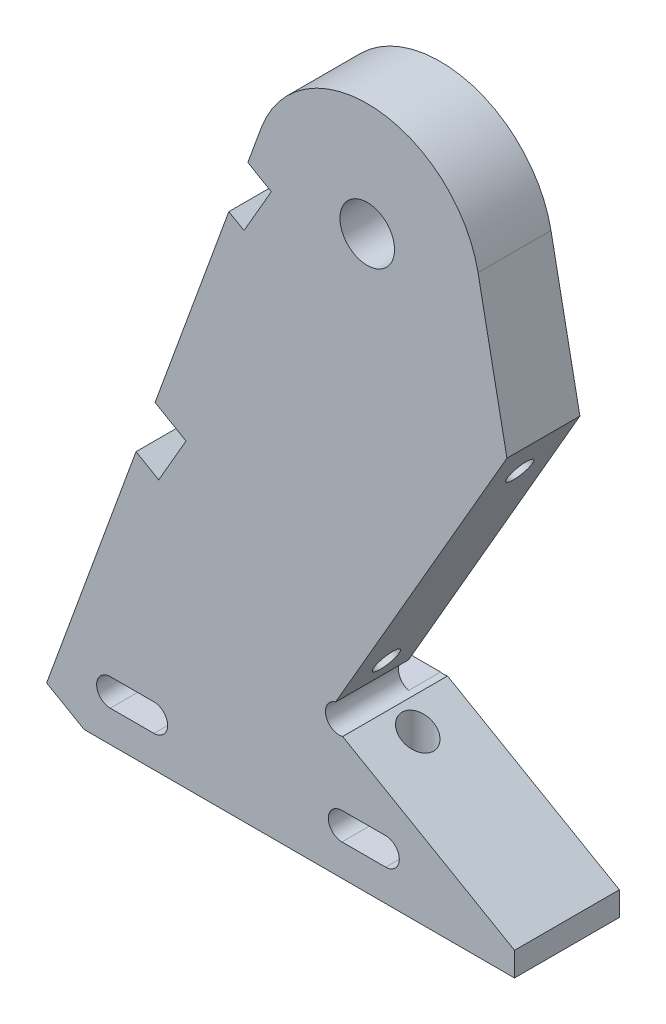
SolidWorks part; units mm, degrees
ref_plane "Front Plane" through (0, 0, 0) normal (0, 0, 1) x (1, 0, 0)
ref_plane "Top Plane" through (0, 0, 0) normal (0, 1, 0) x (1, 0, 0)
ref_plane "Right Plane" through (0, 0, 0) normal (1, 0, 0) x (0, 0, -1)
sketch "Model" plane through (0, 0, 0) normal (0, 0, 1) x (1, 0, 0)
  line L0 (30.032, -29.5212) -> (30.032, -26.7298)
  line L1 (-3.1895, 31.0479) -> (-11.7681, 7.5374)
  line L2 (12.4426, -6.5562) -> (9.2271, -12.1257) construction
  line L3 (16.6788, -19.0204) -> (10.0488, -15.1925) construction
  line L4 (9.6915, -11.3213) -> (10.8533, -15.657) construction
  line L5 (10.2724, -13.4891) -> (9.0035, -13.8291) construction
  line L6 (29.1519, 22.385) -> (9.2271, -12.1257)
  line L7 (30.032, -26.7298) -> (10.0488, -15.1925)
  line L8 (9.3745, -14.8032) -> (2.5284, -10.8506) construction
  line L9 (9.0235, -12.4784) -> (5.2305, -19.0481) construction
  line L10 (0.5709, 41.3535) -> (-0.9796, 37.1044)
  line L11 (0.0253, 32.858) -> (-15.4747, 6.0112) construction
  line L12 (-11.7681, 7.5374) -> (-8.1659, 5.4577)
  line L13 (-15.4747, 6.0112) -> (10.9052, -9.2192) construction
  line L14 (-11.7681, 7.5374) -> (-13.8872, 8.7609) construction
  line L15 (-11.3408, -0.0416) -> (-13.978, 1.4809) construction
  line L16 (-8.1659, 5.4577) -> (-11.3408, -0.0416)
  line L17 (-11.3408, -0.0416) -> (-13.978, 1.4809)
  line L18 (-13.978, 1.4809) -> (-24.3737, -27.0097)
  line L19 (0.0253, 32.858) -> (26.4052, 17.6276) construction
  line L20 (-1.4214, 30.0271) -> (1.7536, 35.5264)
  line L21 (-0.9796, 37.1044) -> (1.7536, 35.5264)
  line L22 (-3.1895, 31.0479) -> (-1.4214, 30.0271)
  line L23 (11.3113, 26.3421) -> (-4.1887, -0.5047) construction
  line L24 (3.5613, 12.9187) -> (-2.5691, 16.458) construction
  line L25 (12.2357, 35.6885) -> (0.2074, 14.855) construction
  line L26 (0.2074, 14.855) -> (12.9074, 36.8521) construction
  line L28 (29.1519, 22.385) -> (25.7905, 39.3975)
  line L80 (-20.0226, -29.5212) -> (-24.3737, -27.0097)
  line L82 (30.032, -29.5212) -> (-20.0226, -29.5212)
  circle A0 centre (12.9074, 36.8521) radius 3.175
  arc A2 (9.2271, -12.1257) -> (10.0488, -15.1925) centre (9.638, -13.6591) ccw
  arc A3 (25.7905, 39.3975) -> (0.5709, 41.3535) centre (12.9074, 36.8521) ccw
  point P11 (8.1045, -14.07)
  point P12 (8.1045, -14.07)
  point P37 (0.1661, 32.7767)
  dimension "D1" = 3.175
  dimension "D7" = 6.35
  dimension "D2" = 31
  dimension "D3" = 3.175
  dimension "D4" = 3.175
  dimension "D5" = 6.35
  dimension "D6" = 25.4
extrude "Boss-Extrude1" add sketch "Model" along normal blind 8.4836
hole_wizard "#4 Clearance Hole3" positions "Sketch8" profile "Sketch9" hole size "#4" standard "ANSI Inch" end condition through all
sketch "Sketch8" plane through (-14.0682, 8.1223, 0) normal (-0.866, 0.5, 0) x (0, 0, 1)
  line L0 (8.4836, 25.2935) -> (0, 31.6435) construction
  point P7 (4.2418, 28.4685)
sketch "Sketch9" plane through (0.1661, 32.7767, 4.2418) normal (0, 0, 1) x (-0.5, -0.866, 0)
  line L0 (0, 0) -> (0, 57.0136)
  line L1 (0, 57.0136) -> (1.4732, 57.0136)
  line L2 (1.4732, 57.0136) -> (1.4732, 0)
  line L5 (1.4732, 0) -> (0, 0)
  line L11 (0, -6.35) -> (0, 107.95) construction
  dimension "Thru Hole Dia." = 2.9464
  dimension "Thru Hole Depth" = 57.0136
hole_wizard "#4 Clearance Hole4" positions "Sketch10" profile "Sketch11" hole size "#4" standard "ANSI Inch" end condition through all
sketch "Sketch10" plane through (-8.4878, 4.9001, 0) normal (-0.866, 0.5, 0) x (0, 0, 1)
  line L0 (0, 0.6438) -> (8.4836, -5.7062) construction
  point P7 (4.2418, -2.5312)
sketch "Sketch11" plane through (-9.7533, 2.708, 4.2418) normal (0, 0, 1) x (-0.5, -0.866, 0)
  line L0 (0, 0) -> (0, 50.5695)
  line L1 (0, 50.5695) -> (1.4732, 50.5695)
  line L2 (1.4732, 50.5695) -> (1.4732, 0)
  line L5 (1.4732, 0) -> (0, 0)
  line L11 (0, -6.35) -> (0, 107.95) construction
  dimension "Thru Hole Dia." = 2.9464
  dimension "Thru Hole Depth" = 50.5695
sketch "Sketch12" plane through (0, 0, 0) normal (0, 0, -1) x (-1, 0, 0)
  line L0 (-59.7491, -15.1956) -> (-12.6102, -15.1956) construction
  line L1 (20.0226, -29.5212) -> (-30.032, -29.5212) construction
  line L2 (20.063, -15.1956) -> (-9.2387, -15.1956)
  line L3 (13.978, 1.4809) -> (24.3737, -27.0097) construction
  line L4 (-10.0488, -15.1925) -> (-30.032, -26.7298)
  line L5 (-30.032, -26.7298) -> (-30.032, -29.5212)
  line L6 (-30.032, -29.5212) -> (20.0226, -29.5212)
  line L7 (20.0226, -29.5212) -> (24.3737, -27.0097)
  line L8 (24.3737, -27.0097) -> (20.063, -15.1956)
  line L9 (-9.2387, -15.1956) -> (56.9978, -15.1956) construction
  arc A0 (-10.0488, -15.1925) -> (-9.2387, -15.1956) centre (-9.638, -13.6591) ccw
  dimension "D1" = 14.3256
extrude "Boss-Extrude2" add sketch "Sketch12" along normal blind 3.7084
sketch "Sketch14" plane through (0, 0, 8.4836) normal (0, 0, 1) x (1, 0, 0)
  line L0 (-14.4346, -29.5212) -> (-14.4346, -15.1956) construction
  line L1 (-20.0226, -29.5212) -> (30.032, -29.5212) construction
  line L2 (-20.063, -15.1956) -> (9.2387, -15.1956) construction
  line L3 (-20.0226, -29.5212) -> (-20.0226, -19.7811) construction
  line L4 (-29.6838, -24.2634) -> (35.3142, -24.2634) construction
  line L5 (-16.9746, -24.2634) -> (-11.8946, -24.2634) construction
  line L6 (-16.9746, -22.6759) -> (-11.8946, -22.6759)
  line L7 (-16.9746, -25.8509) -> (-11.8946, -25.8509)
  line L8 (9.9662, -24.2634) -> (15.0462, -24.2634) construction
  line L9 (9.9662, -22.6759) -> (15.0462, -22.6759)
  line L10 (9.9662, -25.8509) -> (15.0462, -25.8509)
  arc A0 (-16.9746, -22.6759) -> (-16.9746, -25.8509) centre (-16.9746, -24.2634) ccw
  arc A1 (-11.8946, -25.8509) -> (-11.8946, -22.6759) centre (-11.8946, -24.2634) ccw
  arc A2 (9.9662, -22.6759) -> (9.9662, -25.8509) centre (9.9662, -24.2634) ccw
  arc A3 (15.0462, -25.8509) -> (15.0462, -22.6759) centre (15.0462, -24.2634) ccw
  point P11 (-14.4346, -24.2634)
  point P14 (-14.4346, -24.2634)
  point P21 (12.5062, -24.2634)
  dimension "D4" = 1.5875
  dimension "D1" = 5.588
  dimension "D3" = 5.08
  dimension "D5" = 5.2578
extrude "Cut-Extrude1" cut sketch "Sketch14" against normal through all
hole_wizard "#6 Clearance Hole2" positions "Sketch18" profile "Sketch19" hole size "#6" standard "ANSI Inch"
sketch "Sketch18" plane through (0, -29.5212, 0) normal (0, -1, 0) x (-1, 0, 0)
  point P0 (14.4338, -2.2122)
  point P3 (-12.5069, -2.2122)
sketch "Sketch19" plane through (-14.4338, -29.5212, 2.2122) normal (1, 0, 0) x (0, 0, -1)
  line L0 (0, 0) -> (0, 15.4245)
  line L1 (0, 15.4245) -> (1.8288, 14.3256)
  line L2 (1.8288, 14.3256) -> (1.8288, 0)
  line L5 (1.8288, 0) -> (0, 0)
  line L10 (0, 15.4245) -> (-1.8288, 14.3256) construction
  line L11 (0, -6.35) -> (0, 107.95) construction
  dimension "Hole Dia." = 3.6576
  dimension "Hole Depth" = 14.3256
  dimension "Drill Angle" = 118
